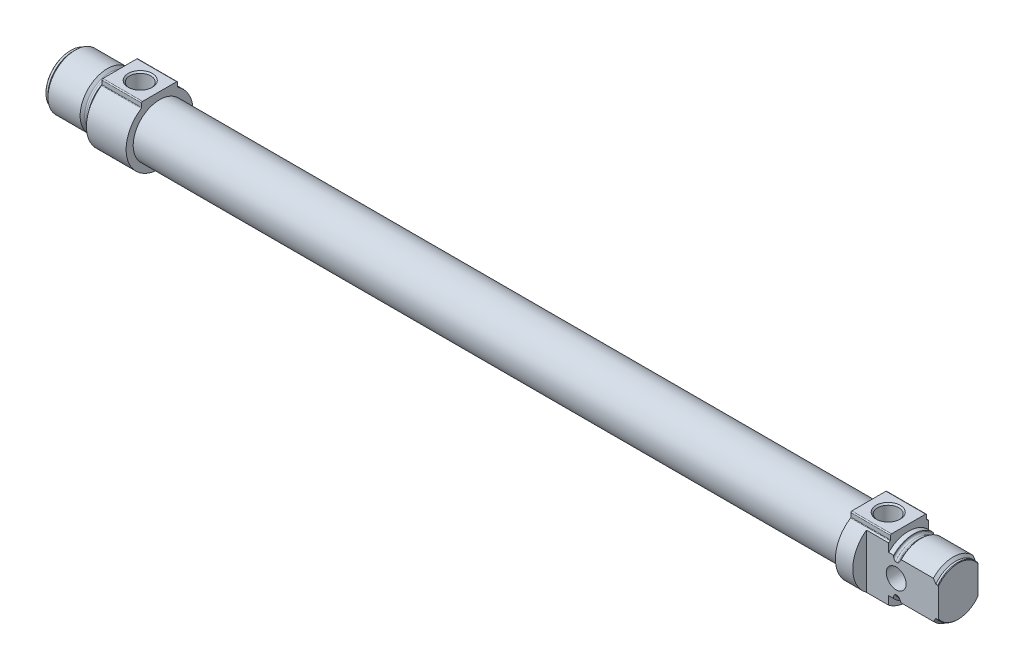
SolidWorks part; units mm, degrees
ref_plane "Front Plane" through (0, 0, 0) normal (0, 0, 1) x (1, 0, 0)
ref_plane "Top Plane" through (0, 0, 0) normal (0, 1, 0) x (1, 0, 0)
ref_plane "Right Plane" through (0, 0, 0) normal (1, 0, 0) x (0, 0, -1)
sketch "Sketch1" plane through (0, 0, 0) normal (0, 0, 1) x (1, 0, 0)
  line L0 (0, 0) -> (0, 9.8)
  line L1 (0, 9.8) -> (0.2, 10)
  line L2 (0.2, 10) -> (1, 10)
  line L3 (1, 10) -> (2, 11)
  line L4 (2, 11) -> (14.95, 11)
  line L5 (14.95, 11) -> (15.8657, 10.0843)
  line L6 (16.4314, 9.85) -> (17.2, 9.85)
  line L7 (18, 10.65) -> (18, 11)
  line L8 (18, 11) -> (20, 11)
  line L9 (20, 11) -> (20, 0)
  line L10 (20, 0) -> (0, 0)
  line L11 (20, 0) -> (0, 0) construction
  arc A0 (15.8657, 10.0843) -> (16.4314, 9.85) centre (16.4314, 10.65) ccw
  arc A1 (17.2, 9.85) -> (18, 10.65) centre (17.2, 10.65) ccw
revolve "Revolve1" add sketch "Sketch1" angle 360 about L11 reverse direction yes
cosmetic thread "Cosmetic Thread1" parameters "D1"=13.87, "D2"=20.16
ref_plane "Plane1" through (28.7, 0, 0) normal (1, 0, 0) x (0, 0, -1)
ref_plane "Plane2" through (10.5, 0, 0) normal (1, 0, 0) x (0, 0, -1)
ref_plane "Plane3" through (0, -14, 0) normal (0, 1, 0) x (1, 0, 0)
ref_plane "Plane4" through (0, 13, 0) normal (0, 1, 0) x (1, 0, 0)
ref_plane "Plane5" through (0, 0, 0) normal (0, 1, 0) x (1, 0, 0)
ref_plane "Plane6" through (0, 0, 0) normal (0, 1, 0) x (1, 0, 0)
ref_plane "Plane7" through (20, 0, 0) normal (1, 0, 0) x (0, 0, -1)
ref_plane "Plane8" through (20, 0, 0) normal (1, 0, 0) x (0, 0, -1)
ref_plane "Plane9" through (33, 0, 0) normal (1, 0, 0) x (0, 0, -1)
ref_plane "Plane10" through (24.5, 0, 0) normal (1, 0, 0) x (0, 0, -1)
ref_plane "Plane11" through (44.5, 0, 0) normal (1, 0, 0) x (0, 0, -1)
sketch "Sketch2" plane through (20, 0, 0) normal (1, 0, 0) x (0, 0, -1)
  line L0 (7.25, 11.5515) -> (7.25, 13.1)
  line L1 (6.85, 13.5) -> (-6.85, 13.5)
  line L2 (-7.25, 13.1) -> (-7.25, 11.5515)
  arc A0 (-7.3859, 11.3004) -> (7.3859, 11.3004) centre (0, 0) ccw
  arc A1 (7.3859, 11.3004) -> (7.25, 11.5515) centre (7.55, 11.5515) cw
  arc A2 (7.25, 13.1) -> (6.85, 13.5) centre (6.85, 13.1) ccw
  arc A3 (-6.85, 13.5) -> (-7.25, 13.1) centre (-6.85, 13.1) ccw
  arc A4 (-7.25, 11.5515) -> (-7.3859, 11.3004) centre (-7.55, 11.5515) cw
extrude "Boss-Extrude1" add sketch "Sketch2" along normal blind 16
ref_plane "Plane12" through (32.5, 0, 0) normal (1, 0, 0) x (0, 0, -1)
ref_plane "Plane13" through (0, 0, 0) normal (0, 0, 1) x (1, 0, 0)
ref_plane "Plane14" through (0, 0, -8.5) normal (0, 0, 1) x (1, 0, 0)
ref_plane "Plane15" through (0, 0, 0) normal (0, 1, 0) x (1, 0, 0)
ref_plane "Plane16" through (0, 6.9, 0) normal (0, 1, 0) x (1, 0, 0)
ref_plane "Plane17" through (0, 0, -6.6) normal (0, 0, 1) x (1, 0, 0)
ref_plane "Plane18" through (0, 0, 0) normal (0, 1, 0) x (1, 0, 0)
ref_plane "Plane19" through (0, 6.9, 0) normal (0, 1, 0) x (1, 0, 0)
ref_plane "Plane20" through (0, 7.8206, -1.379) normal (0, 0.9848, -0.1736) x (1, 0, 0)
ref_plane "Plane21" through (0, 6.3434, -1.1185) normal (0, 0.9848, -0.1736) x (1, 0, 0)
sketch "Sketch3" plane through (0, 0, 0) normal (0, 0, 1) x (1, 0, 0)
  line L0 (36, 0) -> (36, 10.65)
  line L1 (36, 10.65) -> (322, 10.65)
  line L2 (322, 10.65) -> (322, 0)
  line L3 (322, 0) -> (36, 0)
  line L4 (322, 0) -> (36, 0) construction
revolve "Revolve2" add sketch "Sketch3" angle 360 about L4 reverse direction yes
ref_plane "Plane22" through (322, 0, 0) normal (1, 0, 0) x (0, 0, -1)
sketch "Sketch4" plane through (322, 0, 0) normal (1, 0, 0) x (0, 0, -1)
  line L0 (7.25, 11.5515) -> (7.25, 13.1)
  line L1 (6.85, 13.5) -> (-6.85, 13.5)
  line L2 (-7.25, 13.1) -> (-7.25, 11.5515)
  arc A0 (-7.3859, 11.3004) -> (7.3859, 11.3004) centre (0, 0) ccw
  arc A1 (7.3859, 11.3004) -> (7.25, 11.5515) centre (7.55, 11.5515) cw
  arc A2 (7.25, 13.1) -> (6.85, 13.5) centre (6.85, 13.1) ccw
  arc A3 (-6.85, 13.5) -> (-7.25, 13.1) centre (-6.85, 13.1) ccw
  arc A4 (-7.25, 11.5515) -> (-7.3859, 11.3004) centre (-7.55, 11.5515) cw
extrude "Boss-Extrude2" add sketch "Sketch4" along normal blind 16
ref_plane "Plane23" through (325.8, 0, 0) normal (1, 0, 0) x (0, 0, -1)
ref_plane "Plane24" through (325.5, 0, 0) normal (1, 0, 0) x (0, 0, -1)
ref_plane "Plane25" through (0, 0, 6.6) normal (0, 0, 1) x (1, 0, 0)
ref_plane "Plane26" through (0, 0, 0) normal (0, 1, 0) x (1, 0, 0)
ref_plane "Plane27" through (0, 6.9, 0) normal (0, 1, 0) x (1, 0, 0)
ref_plane "Plane28" through (0, 7.8206, 1.379) normal (0, 0.9848, 0.1736) x (1, 0, 0)
ref_plane "Plane29" through (0, 6.3434, 1.1185) normal (0, 0.9848, 0.1736) x (1, 0, 0)
ref_plane "Plane30" through (385, 0, 0) normal (1, 0, 0) x (0, 0, -1)
sketch "Sketch5" plane through (0, 0, 0) normal (0, 0, 1) x (1, 0, 0)
  line L0 (338, 0) -> (338, 11)
  line L1 (338, 11) -> (340, 11)
  line L2 (340, 11) -> (340, 10.65)
  line L3 (340.8, 9.85) -> (341.5686, 9.85)
  line L4 (342.1343, 10.0843) -> (343.05, 11)
  line L5 (343.05, 11) -> (356, 11)
  line L6 (356, 11) -> (357, 10)
  line L7 (357, 10) -> (357.8, 10)
  line L8 (357.8, 10) -> (358, 9.8)
  line L9 (358, 9.8) -> (358, 0)
  line L10 (358, 0) -> (338, 0)
  line L11 (358, 0) -> (338, 0) construction
  arc A0 (340, 10.65) -> (340.8, 9.85) centre (340.8, 10.65) ccw
  arc A1 (341.5686, 9.85) -> (342.1343, 10.0843) centre (341.5686, 10.65) ccw
revolve "Revolve3" add sketch "Sketch5" angle 360 about L11 reverse direction yes
cosmetic thread "Cosmetic Thread2" parameters "D1"=12.87, "D2"=20.16
ref_plane "Plane31" through (372, 0, 0) normal (1, 0, 0) x (0, 0, -1)
ref_plane "Plane32" through (380.5, 0, 0) normal (1, 0, 0) x (0, 0, -1)
ref_plane "Plane33" through (360.5, 0, 0) normal (1, 0, 0) x (0, 0, -1)
sketch "Sketch6" plane through (0, 0, 0) normal (0, 1, 0) x (1, 0, 0)
  line L0 (329, 24) -> (329, 8)
  line L1 (329, 8) -> (358, 8)
  line L2 (358, 8) -> (358, -8)
  line L3 (358, -8) -> (329, -8)
  line L4 (329, -8) -> (329, -24)
  line L5 (329, -24) -> (374, -24)
  line L6 (374, -24) -> (374, 24)
  line L7 (374, 24) -> (329, 24)
extrude "Cut-Extrude1" cut sketch "Sketch6" along normal blind 13.5 and the other way blind 13.5
ref_plane "Plane34" through (341, 0, 0) normal (1, 0, 0) x (0, 0, -1)
hole_wizard "Hole1" positions "Sketch8" profile "Sketch7" legacy
sketch "Sketch8" plane through (0, 0, -8) normal (0, 0, -1) x (-1, 0, 0)
  point P0 (-341, 0)
sketch "Sketch7" plane through (341, 0, -8) normal (1, 0, 0) x (0, 1, 0)
  line L0 (0, 0) -> (0, 16)
  line L1 (0, 16) -> (4, 16)
  line L2 (4, 16) -> (4, 0)
  line L3 (4, 0) -> (0, 0)
  line L4 (0, 110) -> (0, -10) construction
  dimension "Diameter" = 8
  dimension "Depth" = 16
hole_wizard "Hole2" positions "Sketch10" profile "Sketch9" legacy
sketch "Sketch10" plane through (0, 13.5, 0) normal (0, 1, 0) x (1, 0, 0)
  point P0 (28.2, 0)
sketch "Sketch9" plane through (28.2, 13.5, 0) normal (1, 0, 0) x (0, 0, 1)
  line L0 (0, 0) -> (0, 13.5)
  line L1 (0, 13.5) -> (4.283, 13.5)
  line L2 (4.283, 13.5) -> (4.283, 0.581)
  line L3 (4.283, 0.581) -> (4.864, 0)
  line L4 (4.864, 0) -> (0, 0)
  line L5 (0, -6.4453) -> (0, 115.525) construction
  line L6 (-4.283, 0.581) -> (-4.864, 0) construction
  dimension "Diameter" = 8.566
  dimension "Depth" = 13.5
  dimension "C-Sink Angle" = 90
  dimension "C-Sink Diameter" = 9.728
cosmetic thread "Cosmetic Thread3" parameters "D1"=9.5, "D2"=9.728
hole_wizard "Hole3" positions "Sketch12" profile "Sketch11" legacy
sketch "Sketch12" plane through (0, 13.5, 0) normal (0, 1, 0) x (1, 0, 0)
  point P0 (329.8, 0)
sketch "Sketch11" plane through (329.8, 13.5, 0) normal (1, 0, 0) x (0, 0, 1)
  line L0 (0, 0) -> (0, 18.4728)
  line L1 (0, 18.4728) -> (4.283, 16)
  line L2 (4.283, 16) -> (4.283, 0.581)
  line L3 (4.283, 0.581) -> (4.864, 0)
  line L4 (4.864, 0) -> (0, 0)
  line L5 (0, -14.3089) -> (0, 102.4216) construction
  line L6 (0, 18.4728) -> (-4.283, 16) construction
  line L7 (-4.283, 0.581) -> (-4.864, 0) construction
  dimension "Diameter" = 8.566
  dimension "Depth" = 16
  dimension "C-Sink Diameter" = 9.728
  dimension "C-Sink Angle" = 90
  dimension "Drill Angle" = 120
cosmetic thread "Cosmetic Thread4" parameters "D1"=8, "D2"=9.728
sketch "Sketch13" plane through (0, 0, 0) normal (0, 0, 1) x (1, 0, 0)
  line L0 (-4, 0) -> (-4, 4)
  line L1 (-4, 4) -> (50.3, 4)
  line L2 (50.3, 4) -> (50.3, 10)
  line L3 (50.3, 10) -> (305.3, 10)
  line L4 (305.3, 10) -> (305.3, 0)
  line L5 (305.3, 0) -> (-4, 0)
  line L6 (305.3, 0) -> (-4, 0) construction
revolve "Cut-Revolve1" cut sketch "Sketch13" angle 360 about L6 reverse direction yes
ref_plane "Plane35" through (-4, 0, 0) normal (1, 0, 0) x (0, 0, -1)
ref_plane "Plane36" through (0, 13.5, 0) normal (0, 1, 0) x (1, 0, 0)
ref_plane "Plane37" through (6.5, 0, 0) normal (1, 0, 0) x (0, 0, -1)
ref_plane "Plane38" through (0, 0, 0) normal (1, 0, 0) x (0, 0, -1)
ref_plane "Plane39" through (20, 0, 0) normal (1, 0, 0) x (0, 0, -1)
ref_plane "Plane40" through (338, 0, 0) normal (1, 0, 0) x (0, 0, -1)
ref_plane "Plane41" through (20, 0, 0) normal (1, 0, 0) x (0, 0, -1)
ref_plane "Plane42" through (0, 13.5, 0) normal (0, 1, 0) x (1, 0, 0)
ref_plane "Plane43" through (45.5, 0, 0) normal (1, 0, 0) x (0, 0, -1)
ref_plane "Plane44" through (312.5, 0, 0) normal (1, 0, 0) x (0, 0, -1)
ref_plane "Plane45" through (0, 0, 0) normal (0, 0, 1) x (1, 0, 0)
ref_plane "Plane46" through (20, 0, 0) normal (1, 0, 0) x (0, 0, -1)
ref_plane "Plane47" through (0, 13.5, 0) normal (0, 1, 0) x (1, 0, 0)
ref_plane "FDT_FRONT XY" through (20, 0, 0) normal (1, 0, 0) x (0, 0, -1)
ref_plane "FDT_FRONT XZ" through (0, 0, 0) normal (0, -1, 0) x (-1, 0, 0)
ref_plane "FDT_FRONT YZ" through (0, 0, 0) normal (0, 0, -1) x (-1, 0, 0)
ref_axis "FDT_FRONT X" through (20, 0, 80.9) along (0, 0, -1)
ref_axis "FDT_FRONT Y" through (20, -50, 0) along (0, 1, 0)
ref_axis "FDT_FRONT Z" through (80.9, 0, 0) along (-1, 0, 0)
sketch3d "FDT_FRONT"
  point P0 (20, 0, 0)
ref_plane "FDT_QSFRONT XY" through (0, 13.5, 0) normal (0, 1, 0) x (1, 0, 0)
ref_plane "FDT_QSFRONT XZ" through (28.2, 0, 0) normal (-1, 0, 0) x (0, 0, 1)
ref_plane "FDT_QSFRONT YZ" through (0, 0, 0) normal (0, 0, 1) x (1, 0, 0)
ref_axis "FDT_QSFRONT X" through (28.2, 13.5, -50) along (0, 0, 1)
ref_axis "FDT_QSFRONT Y" through (-80.9, 13.5, 0) along (1, 0, 0)
ref_axis "FDT_QSFRONT Z" through (28.2, 50, 0) along (0, -1, 0)
sketch3d "FDT_QSFRONT"
  point P0 (28.2, 13.5, 0)
ref_plane "FDT_QSREAR XY" through (0, 13.5, 0) normal (0, 1, 0) x (1, 0, 0)
ref_plane "FDT_QSREAR XZ" through (329.8, 0, 0) normal (-1, 0, 0) x (0, 0, 1)
ref_plane "FDT_QSREAR YZ" through (0, 0, 0) normal (0, 0, 1) x (1, 0, 0)
ref_axis "FDT_QSREAR X" through (329.8, 13.5, -50) along (0, 0, 1)
ref_axis "FDT_QSREAR Y" through (-80.9, 13.5, 0) along (1, 0, 0)
ref_axis "FDT_QSREAR Z" through (329.8, 50, 0) along (0, -1, 0)
sketch3d "FDT_QSREAR"
  point P0 (329.8, 13.5, 0)
ref_plane "FDT_REAR XY" through (338, 0, 0) normal (-1, 0, 0) x (0, 0, 1)
ref_plane "FDT_REAR XZ" through (0, 0, 0) normal (0, 1, 0) x (1, 0, 0)
ref_plane "FDT_REAR YZ" through (0, 0, 0) normal (0, 0, -1) x (-1, 0, 0)
ref_axis "FDT_REAR X" through (338, 0, 80.9) along (0, 0, -1)
ref_axis "FDT_REAR Y" through (338, 50, 0) along (0, -1, 0)
ref_axis "FDT_REAR Z" through (-80.9, 0, 0) along (1, 0, 0)
sketch3d "FDT_REAR"
  point P0 (338, 0, 0)
ref_plane "FDT_SMBR1 XY" through (45.5, 0, 0) normal (-1, 0, 0) x (0, 0, 1)
ref_plane "FDT_SMBR1 XZ" through (0, 0, 0) normal (0, -1, 0) x (-1, 0, 0)
ref_plane "FDT_SMBR1 YZ" through (0, 0, 0) normal (0, 0, 1) x (1, 0, 0)
ref_axis "FDT_SMBR1 X" through (45.5, 0, -80.9) along (0, 0, 1)
ref_axis "FDT_SMBR1 Y" through (45.5, -50, 0) along (0, 1, 0)
ref_axis "FDT_SMBR1 Z" through (-80.9, 0, 0) along (1, 0, 0)
sketch3d "FDT_SMBR1"
  point P0 (45.5, 0, 0)
ref_plane "FDT_SMBR2 XY" through (312.5, 0, 0) normal (-1, 0, 0) x (0, 0, 1)
ref_plane "FDT_SMBR2 XZ" through (0, 0, 0) normal (0, -1, 0) x (-1, 0, 0)
ref_plane "FDT_SMBR2 YZ" through (0, 0, 0) normal (0, 0, 1) x (1, 0, 0)
ref_axis "FDT_SMBR2 X" through (312.5, 0, -80.9) along (0, 0, 1)
ref_axis "FDT_SMBR2 Y" through (312.5, -50, 0) along (0, 1, 0)
ref_axis "FDT_SMBR2 Z" through (-80.9, 0, 0) along (1, 0, 0)
sketch3d "FDT_SMBR2"
  point P0 (312.5, 0, 0)
ref_plane "FDT_SWIVELAXIS XY" through (0, 0, 0) normal (0, 0, 1) x (1, 0, 0)
ref_plane "FDT_SWIVELAXIS XZ" through (0, 0, 0) normal (0, -1, 0) x (-1, 0, 0)
ref_plane "FDT_SWIVELAXIS YZ" through (341, 0, 0) normal (1, 0, 0) x (0, 0, -1)
ref_axis "FDT_SWIVELAXIS X" through (-80.9, 0, 0) along (1, 0, 0)
ref_axis "FDT_SWIVELAXIS Y" through (341, -50, 0) along (0, 1, 0)
ref_axis "FDT_SWIVELAXIS Z" through (341, 0, 80.9) along (0, 0, -1)
sketch3d "FDT_SWIVELAXIS"
  point P0 (341, 0, 0)
ref_plane "NUT XY" through (6.5, 0, 0) normal (1, 0, 0) x (0, 0, -1)
ref_plane "NUT XZ" through (0, 0, 0) normal (0, -1, 0) x (-1, 0, 0)
ref_plane "NUT YZ" through (0, 0, 0) normal (0, 0, -1) x (-1, 0, 0)
ref_axis "NUT X" through (6.5, 0, 80.9) along (0, 0, -1)
ref_axis "NUT Y" through (6.5, -50, 0) along (0, 1, 0)
ref_axis "NUT Z" through (80.9, 0, 0) along (-1, 0, 0)
sketch3d "NUT"
  point P0 (6.5, 0, 0)
ref_plane "ZR XY" through (0, 0, 0) normal (-1, 0, 0) x (0, 0, 1)
ref_plane "ZR XZ" through (0, 0, 0) normal (0, 1, 0) x (1, 0, 0)
ref_plane "ZR YZ" through (0, 0, 0) normal (0, 0, -1) x (-1, 0, 0)
ref_axis "ZR X" through (0, 0, 80.9) along (0, 0, -1)
ref_axis "ZR Y" through (0, 50, 0) along (0, -1, 0)
ref_axis "ZR Z" through (-80.9, 0, 0) along (1, 0, 0)
sketch3d "ZR"
  point P0 (0, 0, 0)
ref_plane "ZYL XY" through (20, 0, 0) normal (1, 0, 0) x (0, 0, -1)
ref_plane "ZYL XZ" through (0, 0, 0) normal (0, -1, 0) x (-1, 0, 0)
ref_plane "ZYL YZ" through (0, 0, 0) normal (0, 0, -1) x (-1, 0, 0)
ref_axis "ZYL X" through (20, 0, 80.9) along (0, 0, -1)
ref_axis "ZYL Y" through (20, -50, 0) along (0, 1, 0)
ref_axis "ZYL Z" through (80.9, 0, 0) along (-1, 0, 0)
sketch3d "ZYL"
  point P0 (20, 0, 0)
